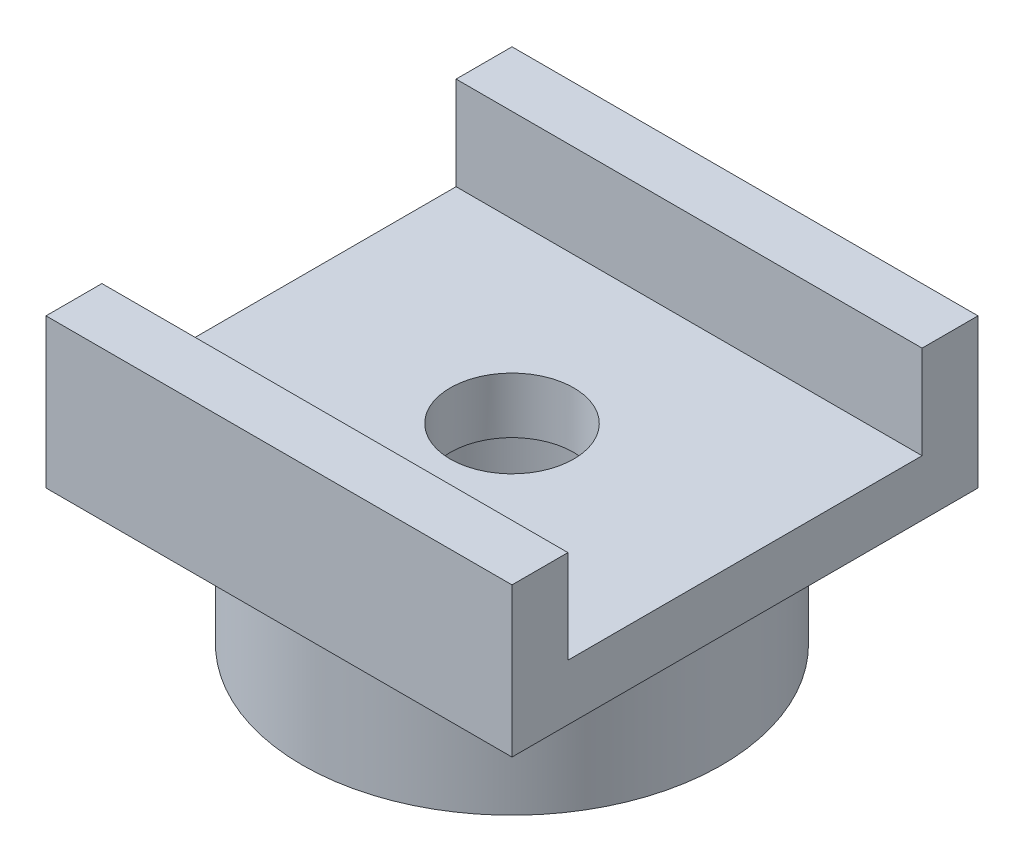
SolidWorks part; units mm, degrees
ref_plane "Plan de face" through (0, 0, 0) normal (0, 0, 1) x (1, 0, 0)
ref_plane "Plan de dessus" through (0, 0, 0) normal (0, 1, 0) x (1, 0, 0)
ref_plane "Plan de droite" through (0, 0, 0) normal (1, 0, 0) x (0, 0, -1)
sketch "Esquisse1" plane through (0, 0, 0) normal (0, 1, 0) x (1, 0, 0)
  circle A0 centre (0, 0) radius 4.5
  dimension "D1" = 9
extrude "Boss.-Extru.1" add sketch "Esquisse1" along normal blind 2.9
sketch "Esquisse2" plane through (0, 2.9, 0) normal (0, 1, 0) x (1, 0, 0)
  line L1 (-5, -5) -> (5, -5)
  line L2 (-5, -5) -> (-5, 5)
  line L3 (-5, 5) -> (5, 5)
  line L4 (5, -5) -> (5, 5)
  line L5 (-5, -5) -> (5, 5) construction
  line L6 (-5, 5) -> (5, -5) construction
  point P0 (0, 0)
  dimension "D1" = 10
  dimension "D2" = 10
extrude "Boss.-Extru.2" add sketch "Esquisse2" along normal blind 1.2
sketch "Esquisse3" plane through (0, 4.1, 0) normal (0, 1, 0) x (1, 0, 0)
  line L0 (5, -5) -> (5, 5) construction
  line L1 (-5, 5) -> (5, 5)
  line L2 (-5, 5) -> (-5, 3.8)
  line L3 (-5, 3.8) -> (5, 3.8)
  line L4 (5, 5) -> (5, 3.8)
  line L6 (-5, -5) -> (5, -5)
  line L7 (-5, -5) -> (-5, -3.8)
  line L8 (-5, -3.8) -> (5, -3.8)
  line L9 (5, -5) -> (5, -3.8)
  dimension "D1" = 1.2
  dimension "D2" = 1.2
extrude "Boss.-Extru.3" add sketch "Esquisse3" along normal blind 2
sketch "Esquisse4" plane through (0, 4.1, 0) normal (0, 1, 0) x (1, 0, 0)
  circle A0 centre (0, 0) radius 1.325
  dimension "D1" = 2.65
extrude "Enlèv. mat.-Extru.1" cut sketch "Esquisse4" against normal blind 10
sketch "Esquisse5" plane through (0, 0, 0) normal (0, -1, 0) x (-1, 0, 0)
  circle A0 centre (0, 0) radius 2.625
  dimension "D1" = 5.25
extrude "Enlèv. mat.-Extru.2" cut sketch "Esquisse5" against normal up to surface (2.9 mm away) up to face at (0, 2.9, 4.5)
